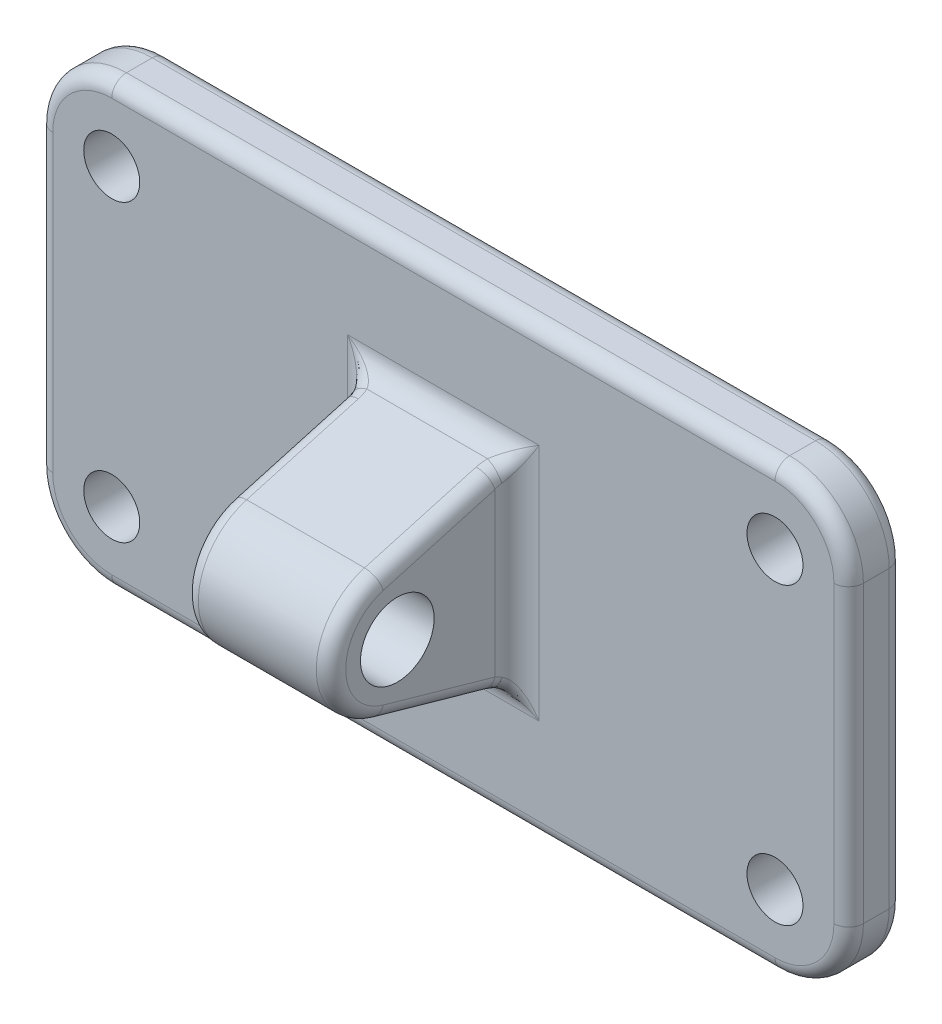
SolidWorks part; units mm, degrees
ref_plane "Front Plane" through (0, 0, 0) normal (0, 0, 1) x (1, 0, 0)
ref_plane "Top Plane" through (0, 0, 0) normal (0, 1, 0) x (1, 0, 0)
ref_plane "Right Plane" through (0, 0, 0) normal (1, 0, 0) x (0, 0, -1)
sketch "Sketch1" plane through (0, 0, 0) normal (0, 0, 1) x (1, 0, 0)
  line L0 (-57.15, 25.4) -> (57.15, 25.4) construction
  line L1 (-69.85, -38.1) -> (69.85, -38.1)
  line L2 (-69.85, -38.1) -> (-69.85, 38.1)
  line L3 (-69.85, 38.1) -> (69.85, 38.1)
  line L4 (69.85, -38.1) -> (69.85, 38.1)
  line L5 (-69.85, -38.1) -> (69.85, 38.1) construction
  line L6 (-69.85, 38.1) -> (69.85, -38.1) construction
  line L7 (57.15, -25.4) -> (57.15, 25.4) construction
  line L8 (-57.15, -25.4) -> (57.15, -25.4) construction
  line L9 (-57.15, -25.4) -> (-57.15, 25.4) construction
  circle A0 centre (-57.15, 25.4) radius 4.826
  circle A1 centre (57.15, 25.4) radius 4.826
  circle A2 centre (57.15, -25.4) radius 4.826
  circle A3 centre (-57.15, -25.4) radius 4.826
  point P0 (0, 0)
  dimension "D4" = 9.652
  dimension "D1" = 139.7
  dimension "D2" = 76.2
  dimension "D3" = 12.7
extrude "Boss-Extrude1" add sketch "Sketch1" along normal mid plane 9.525
sketch "Sketch2" plane through (0, 0, 0) normal (1, 0, 0) x (0, 0, -1)
  line L0 (0, -19.05) -> (0, 19.05)
  line L1 (0, 0) -> (-25.4, 0) construction
  line L2 (0, -19.05) -> (-28.5063, -10.9998)
  line L3 (0, 19.05) -> (-28.5063, 10.9998)
  circle A0 centre (-25.4, 0) radius 6.35
  arc A1 (-28.5063, 10.9998) -> (-28.5063, -10.9998) centre (-25.4, 0) ccw
  point P4 (0, 0)
  dimension "D3" = 12.7
  dimension "D4" = 22.86
  dimension "D1" = 38.1
  dimension "D2" = 25.4
extrude "Boss-Extrude2" add sketch "Sketch2" along normal mid plane 25.4
fillet "Fillet1" radius 12.7 4 edges at (-69.85, 38.1, 0) (-69.85, -38.1, 0) (69.85, 38.1, 0) (69.85, -38.1, 0)
fillet "Fillet2" radius 2.54 16 edges at (-66.1303, -34.3803, -4.7625) (-69.85, 0, -4.7625) (-66.1303, 34.3803, -4.7625) (0, 38.1, -4.7625) (66.1303, 34.3803, -4.7625) (69.85, 0, -4.7625) (66.1303, -34.3803, -4.7625) (-66.1303, -34.3803, 4.7625) (-69.85, 0, 4.7625) (-66.1303, 34.3803, 4.7625) (0, 38.1, 4.7625) (66.1303, 34.3803, 4.7625) (69.85, 0, 4.7625) (66.1303, -34.3803, 4.7625) (0, -38.1, -4.7625) (0, -38.1, 4.7625)
fillet "Fillet3" radius 3.81 4 edges at (-12.7, 0, 4.7625) (0, 17.7051, 4.7625) (12.7, 0, 4.7625) (0, -17.7051, 4.7625)
fillet "Fillet4" radius 2.54 14 edges at (-14.211, 18.2891, 5.5343) (-12.736, 16.7767, 8.0498) (-12.7, 13.8145, 18.5394) (-12.7, 0, 36.83) (-14.211, -18.2891, 5.5343) (-12.736, -16.7767, 8.0498) (14.211, 18.2891, 5.5343) (12.736, 16.7767, 8.0498) (12.7, 13.8145, 18.5394) (12.7, 0, 36.83) (14.211, -18.2891, 5.5343) (12.736, -16.7767, 8.0498) (-12.7, -13.8145, 18.5394) (12.7, -13.8145, 18.5394)
